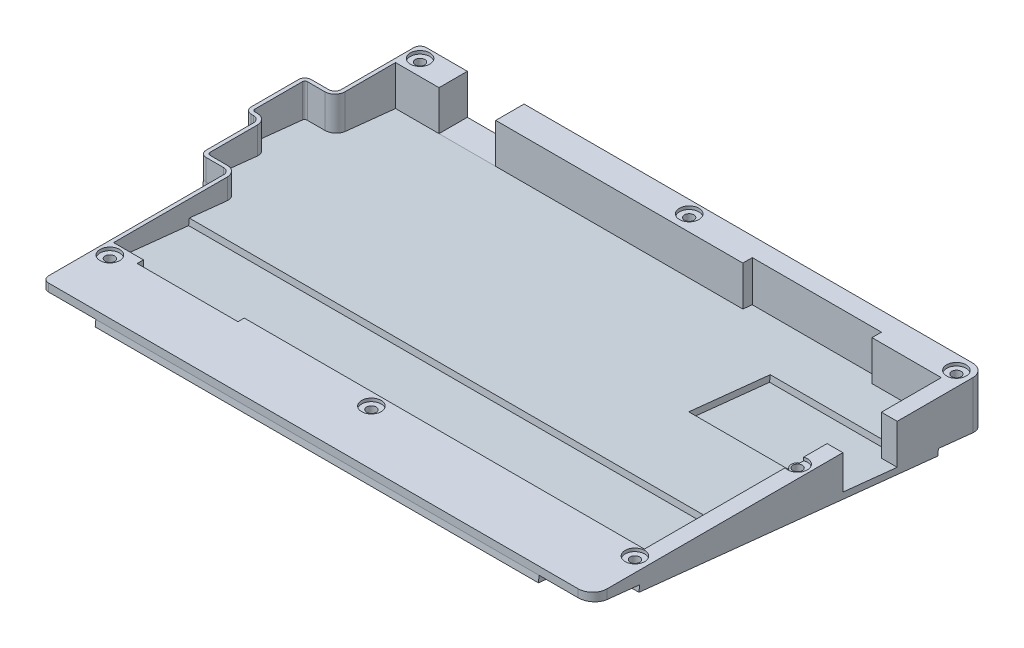
SolidWorks part; units mm, degrees
ref_plane "Front Plane" through (0, 0, 0) normal (0, 0, 1) x (1, 0, 0)
ref_plane "Top Plane" through (0, 0, 0) normal (0, 1, 0) x (1, 0, 0)
ref_plane "Right Plane" through (0, 0, 0) normal (1, 0, 0) x (0, 0, -1)
sketch "Sketch1" plane through (0, 0, 0) normal (0, 1, 0) x (1, 0, 0)
  line L0 (138.4196, 31.7518) -> (125.4196, 31.7518)
  line L1 (-35.0204, 31.7518) -> (107.4196, 31.7518)
  line L2 (140.4196, 29.7518) -> (140.4196, 6.7018)
  line L3 (-34.0204, 3.7518) -> (-34.0204, 22.7518)
  line L4 (136.4596, 27.7518) -> (136.4396, 27.7518)
  line L5 (142.4196, 4.7018) -> (147.9496, 4.7018)
  line L6 (-34.0204, 22.7518) -> (-12.0204, 22.7518)
  line L8 (149.9496, 2.7018) -> (149.9496, -12.3482)
  line L11 (147.9496, -14.3482) -> (147.1896, -14.3482)
  line L14 (145.1896, -16.3482) -> (145.1896, -31.3982)
  line L17 (143.1896, -33.3982) -> (137.6696, -33.3982)
  line L20 (135.6696, -35.3982) -> (135.6696, -77.4982)
  line L21 (-34.0204, -25.6003) -> (-34.0204, -71.4982)
  line L23 (133.6696, -79.4982) -> (-35.0204, -79.4982)
  line L28 (-39.0204, 27.7518) -> (-39.0204, 3.7518)
  line L31 (-34.0204, 3.7518) -> (-39.0204, 3.7518)
  line L32 (-34.0204, -13.4982) -> (-39.0204, -13.4982)
  line L33 (-39.0204, -75.4982) -> (-39.0204, -13.4982)
  line L34 (-34.0204, -71.4982) -> (92.9796, -71.4982)
  line L35 (92.9796, -71.4982) -> (92.9796, -73.4982)
  line L36 (92.9796, -73.4982) -> (124.9796, -73.4982)
  line L37 (124.9796, -73.4982) -> (124.9796, -71.4982)
  line L39 (134.4706, -35.3982) -> (134.4706, -71.4982)
  line L40 (134.4706, -71.4982) -> (124.9796, -71.4982)
  line L41 (137.6696, -32.1992) -> (143.1896, -32.1992)
  line L42 (-34.0204, -13.4982) -> (-34.0204, -22.1362)
  line L43 (143.9906, -31.3982) -> (143.9906, -16.3482)
  line L44 (-12.0204, 22.7518) -> (-12.0204, 25.7518)
  line L45 (147.1896, -13.1492) -> (147.9496, -13.1492)
  line L46 (148.7506, -12.3482) -> (148.7506, 2.7018)
  line L47 (-12.0204, 25.7518) -> (28.9796, 25.7518)
  line L48 (28.9796, 25.7518) -> (28.9796, 22.7518)
  line L49 (28.9796, 22.7518) -> (107.4196, 22.7518)
  line L50 (147.9496, 3.5027) -> (142.4196, 3.5027)
  line L51 (107.4196, 22.7518) -> (107.4196, 31.7518)
  line L52 (139.2206, 6.7018) -> (139.2206, 22.7518)
  line L53 (125.4196, 31.7518) -> (125.4196, 22.7518)
  line L54 (139.2206, 22.7518) -> (125.4196, 22.7518)
  arc A0 (138.4196, 31.7518) -> (140.4196, 29.7518) centre (138.4196, 29.7518) cw
  arc A1 (140.4196, 6.7018) -> (142.4196, 4.7018) centre (142.4196, 6.7018) ccw
  arc A2 (149.9496, 2.7018) -> (147.9496, 4.7018) centre (147.9496, 2.7018) ccw
  arc A3 (149.9496, -12.3482) -> (147.9496, -14.3482) centre (147.9496, -12.3482) cw
  arc A4 (147.1896, -14.3482) -> (145.1896, -16.3482) centre (147.1896, -16.3482) ccw
  arc A5 (145.1896, -31.3982) -> (143.1896, -33.3982) centre (143.1896, -31.3982) cw
  arc A6 (-35.0204, 31.7518) -> (-39.0204, 27.7518) centre (-35.0204, 27.7518) ccw
  arc A7 (-39.0204, -75.4982) -> (-35.0204, -79.4982) centre (-35.0204, -75.4982) ccw
  arc A8 (133.6696, -79.4982) -> (135.6696, -77.4982) centre (133.6696, -77.4982) ccw
  arc A9 (135.6696, -35.3982) -> (137.6696, -33.3982) centre (137.6696, -35.3982) cw
  circle A10 centre (-34.4204, 27.1518) radius 1.1
  circle A11 centre (51.0096, 27.7518) radius 1.1
  circle A12 centre (136.4396, 27.7518) radius 1.1
  circle A13 centre (-34.4204, -74.8982) radius 1.1
  circle A14 centre (48.6296, -75.4982) radius 1.1
  circle A15 centre (131.6496, -75.4982) radius 1.1
  circle A16 centre (-35.0204, -23.8682) radius 1.1
  arc A27 (-34.0204, -22.1362) -> (-34.0204, -25.6003) centre (-35.0204, -23.8682) cw
  arc A28 (139.2206, 6.7018) -> (142.4196, 3.5027) centre (142.4196, 6.7018) ccw
  arc A29 (147.9496, 3.5027) -> (148.7506, 2.7018) centre (147.9496, 2.7018) cw
  arc A30 (148.7506, -12.3482) -> (147.9496, -13.1492) centre (147.9496, -12.3482) cw
  arc A31 (147.1896, -13.1492) -> (143.9906, -16.3482) centre (147.1896, -16.3482) ccw
  arc A32 (143.9906, -31.3982) -> (143.1896, -32.1992) centre (143.1896, -31.3982) cw
  arc A33 (137.6696, -32.1992) -> (134.4706, -35.3982) centre (137.6696, -35.3982) ccw
extrude "Boss-Extrude2" add sketch "Sketch1" against normal blind 4.7 contours L41 A33 L39 L40 L37 L36 L35 L34 L21 A27 L42 L32 L33 A7 L23 A8 L20 A9 L17 A5 L14 A4 L11 A3 L8 A2 L5 A1 L2 A0 L0 L53 L54 L52 A28 L50 A29 L46 A30 L45 A31 L43 A32 A12 A13 A14 A15 | L1 A6 L28 L31 L3 L6 L44 L47 L48 L49 L51 A11 A10 region at (138.2833, 0, -29.6154) region at (31.7683, 0, -26.4895)
move or copy body "Body-Move/Copy1" bodies to move or copy 105 104 copy no rotation origin (55.4646, -2.35, 0) rotation axis (0, 0, 1) rotation angle 180
sketch "Sketch3" plane through (149.9496, 0, 0) normal (1, 0, 0) x (0, 0, -1)
  line L0 (-79.4982, 0) -> (-79.4982, -4.7) construction
  line L1 (-79.4982, 0) -> (-79.4982, -4.7)
  line L2 (31.7518, 0) -> (31.7518, -4.7) construction
  line L3 (31.7518, 0) -> (31.7518, -4.7)
  line L5 (-79.4982, -4.7) -> (31.7518, -16.3928)
  line L6 (31.7518, -16.3928) -> (31.7518, -4.7)
  line L7 (31.7518, -4.7) -> (-79.4982, -4.7)
  line M3 (-75.4982, -4.7) -> (-13.4982, -4.7)
  dimension "D1" = 6
extrude "Boss-Extrude3" add sketch "Sketch3" against normal up to surface (188.97 mm away) contours L6 L7 L5 M3 region at (149.9496, -8.5976, 5.3315) up to face at (-39.0204, -2.35, 4.8232)
sketch "Sketch4" plane through (0, -4.7, 0) normal (0, 1, 0) x (1, 0, 0)
  line L2 (145.9496, -79.4982) -> (149.9496, -79.4982)
  line L3 (149.9496, -79.4982) -> (149.9496, -75.4982)
  line L4 (-29.4904, 6.7018) -> (-29.4904, 29.7518)
  line L5 (-27.4904, 31.7518) -> (-39.0204, 31.7518)
  line L6 (-36.2604, -14.3482) -> (-37.0204, -14.3482)
  line L7 (-39.0204, -12.3482) -> (-39.0204, -79.4982)
  line L8 (-39.0204, -79.4982) -> (-22.7404, -79.4982)
  line L9 (-24.7404, -77.4982) -> (-24.7404, -35.3982)
  line L10 (-26.7404, -33.3982) -> (-32.2604, -33.3982)
  line L11 (-34.2604, -31.3982) -> (-34.2604, -16.3482)
  line L12 (-36.2604, -14.3482) -> (-37.0204, -14.3482)
  line L13 (-39.0204, -12.3482) -> (-39.0204, -79.4982)
  line L14 (-39.0204, -79.4982) -> (-22.7404, -79.4982)
  line L15 (-24.7404, -77.4982) -> (-24.7404, -35.3982)
  line L16 (-26.7404, -33.3982) -> (-32.2604, -33.3982)
  line L17 (-34.2604, -31.3982) -> (-34.2604, -16.3482)
  line L18 (-39.0204, 31.7518) -> (-39.0204, 2.7018)
  line L19 (-37.0204, 4.7018) -> (-31.4904, 4.7018)
  line L20 (-29.4904, 6.7018) -> (-29.4904, 29.7518)
  line L21 (-27.4904, 31.7518) -> (-39.0204, 31.7518)
  line L22 (-39.0204, 31.7518) -> (-39.0204, 2.7018)
  line L23 (-37.0204, 4.7018) -> (-31.4904, 4.7018)
  line L24 (145.9496, -79.4982) -> (149.9496, -79.4982)
  line L25 (149.9496, -79.4982) -> (149.9496, -75.4982)
  line L26 (149.9496, 31.7518) -> (145.9496, 31.7518)
  line L27 (149.9496, 27.7518) -> (149.9496, 31.7518)
  line L28 (149.9496, 31.7518) -> (145.9496, 31.7518)
  line L29 (149.9496, 27.7518) -> (149.9496, 31.7518)
  arc A1 (145.9496, -79.4982) -> (149.9496, -75.4982) centre (145.9496, -75.4982) ccw
  arc A2 (145.9496, -79.4982) -> (149.9496, -75.4982) centre (145.9496, -75.4982) ccw
  arc A3 (-27.4904, 31.7518) -> (-29.4904, 29.7518) centre (-27.4904, 29.7518) ccw
  arc A4 (-37.0204, 4.7018) -> (-39.0204, 2.7018) centre (-37.0204, 2.7018) ccw
  arc A5 (-39.0204, -12.3482) -> (-37.0204, -14.3482) centre (-37.0204, -12.3482) ccw
  arc A6 (-24.7404, -77.4982) -> (-22.7404, -79.4982) centre (-22.7404, -77.4982) ccw
  arc A7 (-24.7404, -35.3982) -> (-26.7404, -33.3982) centre (-26.7404, -35.3982) ccw
  arc A8 (-34.2604, -31.3982) -> (-32.2604, -33.3982) centre (-32.2604, -31.3982) ccw
  arc A9 (-34.2604, -16.3482) -> (-36.2604, -14.3482) centre (-36.2604, -16.3482) ccw
  arc A10 (-39.0204, -12.3482) -> (-37.0204, -14.3482) centre (-37.0204, -12.3482) ccw
  arc A11 (-24.7404, -77.4982) -> (-22.7404, -79.4982) centre (-22.7404, -77.4982) ccw
  arc A12 (-24.7404, -35.3982) -> (-26.7404, -33.3982) centre (-26.7404, -35.3982) ccw
  arc A13 (-34.2604, -31.3982) -> (-32.2604, -33.3982) centre (-32.2604, -31.3982) ccw
  arc A14 (-34.2604, -16.3482) -> (-36.2604, -14.3482) centre (-36.2604, -16.3482) ccw
  arc A15 (-31.4904, 4.7018) -> (-29.4904, 6.7018) centre (-31.4904, 6.7018) ccw
  arc A16 (-27.4904, 31.7518) -> (-29.4904, 29.7518) centre (-27.4904, 29.7518) ccw
  arc A17 (-37.0204, 4.7018) -> (-39.0204, 2.7018) centre (-37.0204, 2.7018) ccw
  arc A18 (-31.4904, 4.7018) -> (-29.4904, 6.7018) centre (-31.4904, 6.7018) ccw
  arc A19 (149.9496, 27.7518) -> (145.9496, 31.7518) centre (145.9496, 27.7518) ccw
  arc A20 (149.9496, 27.7518) -> (145.9496, 31.7518) centre (145.9496, 27.7518) ccw
  dimension "D1" = 0
  dimension "D2" = 0
  dimension "D3" = 0
  dimension "D4" = 0
extrude "Cut-Extrude1" cut sketch "Sketch4" against normal through all
ref_plane "Plane4" through (0, 15, 0) normal (0, 1, 0) x (1, 0, 0)
sketch "Sketch10" plane through (0, 15, 0) normal (0, 1, 0) x (1, 0, 0)
  line L0 (-14.4904, 22.7518) -> (3.5096, 22.7518)
  line L1 (144.9496, 3.7518) -> (144.9496, -13.4982)
  line L27 (-14.4904, 31.7518) -> (-14.4904, 22.7518)
  line L28 (-14.4904, 22.7518) -> (-28.2913, 22.7518)
  line L29 (-28.2913, 22.7518) -> (-28.2913, 6.7018)
  line L30 (-31.4904, 3.5027) -> (-37.0204, 3.5027)
  line L31 (-37.8213, 2.7018) -> (-37.8213, -12.3482)
  line L32 (-37.0204, -13.1492) -> (-36.2604, -13.1492)
  line L33 (-33.0613, -16.3482) -> (-33.0613, -31.3982)
  line L34 (-32.2604, -32.1992) -> (-26.7404, -32.1992)
  line L35 (-23.5413, -35.3982) -> (-23.5413, -71.4982)
  line L36 (-23.5413, -71.4982) -> (-14.0504, -71.4982)
  line L37 (-14.0504, -71.4982) -> (-14.0504, -73.4982)
  line L38 (-14.0504, -73.4982) -> (17.9496, -73.4982)
  line L39 (17.9496, -73.4982) -> (17.9496, -71.4982)
  line L40 (17.9496, -71.4982) -> (144.9496, -71.4982)
  line L41 (144.9496, -71.4982) -> (144.9496, -25.6003)
  line L42 (144.9496, -22.1362) -> (144.9496, -13.4982)
  line L43 (144.9496, -13.4982) -> (149.9496, -13.4982)
  line L44 (149.9496, -13.4982) -> (149.9496, 3.7518)
  line L45 (149.9496, 3.7518) -> (144.9496, 3.7518)
  line L46 (144.9496, 3.7518) -> (144.9496, 22.7518)
  line L47 (144.9496, 22.7518) -> (122.9496, 22.7518)
  line L48 (122.9496, 22.7518) -> (122.9496, 25.7518)
  line L49 (122.9496, 25.7518) -> (81.9496, 25.7518)
  line L50 (81.9496, 25.7518) -> (81.9496, 22.7518)
  line L51 (81.9496, 22.7518) -> (3.5096, 22.7518)
  line L52 (3.5096, 22.7518) -> (3.5096, 31.7518)
  line L53 (3.5096, 31.7518) -> (-14.4904, 31.7518)
  line L54 (-14.4904, 31.7518) -> (-14.4904, 22.7518)
  line L55 (-14.4904, 22.7518) -> (-28.2913, 22.7518)
  line L56 (-28.2913, 22.7518) -> (-28.2913, 6.7018)
  line L57 (-31.4904, 3.5027) -> (-37.0204, 3.5027)
  line L58 (-37.8213, 2.7018) -> (-37.8213, -12.3482)
  line L59 (-37.0204, -13.1492) -> (-36.2604, -13.1492)
  line L60 (-33.0613, -16.3482) -> (-33.0613, -31.3982)
  line L61 (-32.2604, -32.1992) -> (-26.7404, -32.1992)
  line L62 (-23.5413, -35.3982) -> (-23.5413, -71.4982)
  line L63 (-23.5413, -71.4982) -> (-14.0504, -71.4982)
  line L64 (-14.0504, -71.4982) -> (-14.0504, -73.4982)
  line L65 (-14.0504, -73.4982) -> (17.9496, -73.4982)
  line L66 (17.9496, -73.4982) -> (17.9496, -71.4982)
  line L67 (17.9496, -71.4982) -> (144.9496, -71.4982)
  line L68 (144.9496, -71.4982) -> (144.9496, -25.6003)
  line L69 (144.9496, -22.1362) -> (144.9496, -13.4982)
  line L70 (144.9496, -13.4982) -> (149.9496, -13.4982)
  line L71 (149.9496, -13.4982) -> (149.9496, 3.7518)
  line L72 (149.9496, 3.7518) -> (144.9496, 3.7518)
  line L73 (144.9496, 3.7518) -> (144.9496, 22.7518)
  line L74 (144.9496, 22.7518) -> (122.9496, 22.7518)
  line L75 (122.9496, 22.7518) -> (122.9496, 25.7518)
  line L76 (122.9496, 25.7518) -> (81.9496, 25.7518)
  line L77 (81.9496, 25.7518) -> (81.9496, 22.7518)
  line L78 (81.9496, 22.7518) -> (3.5096, 22.7518)
  line L79 (3.5096, 22.7518) -> (3.5096, 31.7518)
  line L80 (3.5096, 31.7518) -> (-14.4904, 31.7518)
  arc A7 (-31.4904, 3.5027) -> (-28.2913, 6.7018) centre (-31.4904, 6.7018) ccw
  arc A8 (-37.0204, 3.5027) -> (-37.8213, 2.7018) centre (-37.0204, 2.7018) ccw
  arc A9 (-37.8213, -12.3482) -> (-37.0204, -13.1492) centre (-37.0204, -12.3482) ccw
  arc A10 (-33.0613, -16.3482) -> (-36.2604, -13.1492) centre (-36.2604, -16.3482) ccw
  arc A11 (-33.0613, -31.3982) -> (-32.2604, -32.1992) centre (-32.2604, -31.3982) ccw
  arc A12 (-23.5413, -35.3982) -> (-26.7404, -32.1992) centre (-26.7404, -35.3982) ccw
  arc A13 (144.9496, -22.1362) -> (144.9496, -25.6003) centre (145.9496, -23.8682) ccw
  arc A14 (-31.4904, 3.5027) -> (-28.2913, 6.7018) centre (-31.4904, 6.7018) ccw
  arc A15 (-37.0204, 3.5027) -> (-37.8213, 2.7018) centre (-37.0204, 2.7018) ccw
  arc A16 (-37.8213, -12.3482) -> (-37.0204, -13.1492) centre (-37.0204, -12.3482) ccw
  arc A17 (-33.0613, -16.3482) -> (-36.2604, -13.1492) centre (-36.2604, -16.3482) ccw
  arc A18 (-33.0613, -31.3982) -> (-32.2604, -32.1992) centre (-32.2604, -31.3982) ccw
  arc A19 (-23.5413, -35.3982) -> (-26.7404, -32.1992) centre (-26.7404, -35.3982) ccw
  arc A20 (144.9496, -22.1362) -> (144.9496, -25.6003) centre (145.9496, -23.8682) ccw
  dimension "D1" = 0
extrude "Cut-Extrude2" cut sketch "Sketch10" against normal through all contours A20 L69 L1 L73 L74 L75 L76 L77 L78 L0 L55 L56 A14 L57 A15 L58 A16 L59 A17 L60 A18 L61 A19 L62 L63 L64 L65 L66 L67 L68 region at (57.9798, 15, 23.6888)
sketch "Sketch11" plane through (144.9496, 0, 0) normal (-1, 0, 0) x (0, 0, 1)
  line L0 (-22.7518, -15.4469) -> (71.4982, -5.5408)
  line L1 (71.4982, -5.5408) -> (71.4982, -3.5408)
  line L2 (71.4982, 0) -> (71.4982, -5.5408) construction
  line L3 (71.4982, -3.5408) -> (-22.7518, -13.4469)
  line L4 (-22.7518, 0) -> (-22.7518, -15.4469) construction
  line L5 (-22.7518, -13.4469) -> (-22.7518, -15.4469)
  dimension "D1" = 2
  dimension "D2" = 2
extrude "Boss-Extrude4" add sketch "Sketch11" along normal up to surface (182.7709 mm away)
sketch "Sketch12" plane through (0, -10.9348, 1.1493) normal (0, 0.9945, -0.1045) x (1, 0, 0)
  line L0 (-29.4904, 7.8943) -> (-29.4904, 24.0327) construction
  line L1 (-29.4904, 24.0327) -> (-37.8213, 24.0327) construction
  line L2 (-37.8213, 24.0327) -> (-37.8213, 5.715) construction
  line L3 (-37.0204, 5.8833) -> (-31.4904, 5.8833) construction
  line L4 (-36.2604, -13.2716) -> (-37.0204, -13.2716) construction
  line L5 (-37.8213, -13.1033) -> (-37.8213, -70.7364) construction
  line L6 (-37.8213, -70.7364) -> (-24.7404, -70.7364) construction
  line L7 (-24.7404, -70.7364) -> (-24.7404, -34.4376) construction
  line L8 (-26.7404, -32.4266) -> (-32.2604, -32.4266) construction
  line L9 (-34.2604, -30.4155) -> (-34.2604, -15.2826) construction
  line L10 (-29.4904, 7.8943) -> (-29.4904, 24.0327)
  line L11 (-29.4904, 24.0327) -> (-37.8213, 24.0327)
  line L12 (-37.8213, 24.0327) -> (-37.8213, 5.715)
  line L13 (-37.0204, 5.8833) -> (-31.4904, 5.8833)
  line L14 (-36.2604, -13.2716) -> (-37.0204, -13.2716)
  line L15 (-37.8213, -13.1033) -> (-37.8213, -70.7364)
  line L16 (-37.8213, -70.7364) -> (-24.7404, -70.7364)
  line L17 (-24.7404, -70.7364) -> (-24.7404, -34.4376)
  line L18 (-26.7404, -32.4266) -> (-32.2604, -32.4266)
  line L19 (-34.2604, -30.4155) -> (-34.2604, -15.2826)
  line L20 (-37.8213, 24.0327) -> (-37.8213, 25.9101)
  line L21 (-29.4904, 24.0327) -> (-29.4904, 27.1127)
  line L22 (-29.4904, 27.1127) -> (-37.8213, 25.9101)
  ellipse E0 centre (-31.4904, 7.8943) end of major axis (-31.4904, 9.9053) minor radius 2 (-31.4904, 5.8833) -> (-29.4904, 7.8943) ccw construction
  ellipse E1 centre (-37.0204, 3.8723) end of major axis (-37.0204, 5.8833) minor radius 2 (-37.0204, 5.8833) -> (-37.8213, 5.715) ccw construction
  ellipse E2 centre (-37.0204, -11.2606) end of major axis (-37.0204, -9.2496) minor radius 2 (-37.8213, -13.1033) -> (-37.0204, -13.2716) ccw construction
  ellipse E3 centre (-26.7404, -34.4376) end of major axis (-26.7404, -32.4266) minor radius 2 (-24.7404, -34.4376) -> (-26.7404, -32.4266) ccw construction
  ellipse E4 centre (-32.2604, -30.4155) end of major axis (-32.2604, -28.4045) minor radius 2 (-34.2604, -30.4155) -> (-32.2604, -32.4266) ccw construction
  ellipse E5 centre (-36.2604, -15.2826) end of major axis (-36.2604, -13.2716) minor radius 2 (-34.2604, -15.2826) -> (-36.2604, -13.2716) ccw construction
  ellipse E6 centre (-31.4904, 7.8943) end of major axis (-31.4904, 9.9053) minor radius 2 (-31.4904, 5.8833) -> (-29.4904, 7.8943) ccw
  ellipse E7 centre (-37.0204, 3.8723) end of major axis (-37.0204, 5.8833) minor radius 2 (-37.0204, 5.8833) -> (-37.8213, 5.715) ccw
  ellipse E8 centre (-37.0204, -11.2606) end of major axis (-37.0204, -9.2496) minor radius 2 (-37.8213, -13.1033) -> (-37.0204, -13.2716) ccw
  ellipse E9 centre (-26.7404, -34.4376) end of major axis (-26.7404, -32.4266) minor radius 2 (-24.7404, -34.4376) -> (-26.7404, -32.4266) ccw
  ellipse E10 centre (-32.2604, -30.4155) end of major axis (-32.2604, -28.4045) minor radius 2 (-34.2604, -30.4155) -> (-32.2604, -32.4266) ccw
  ellipse E11 centre (-36.2604, -15.2826) end of major axis (-36.2604, -13.2716) minor radius 2 (-34.2604, -15.2826) -> (-36.2604, -13.2716) ccw
sketch "Sketch26" plane through (-37.8213, 0, 0) normal (-1, 0, 0) x (0, 0, 1)
  line L0 (14.1808, -9.5651) -> (-4.5344, -11.5322)
  line L1 (-4.5344, -13.5322) -> (14.1808, -11.5651)
  line L4 (-22.7518, -15.4469) -> (-4.5344, -13.5322)
  line L5 (-4.5344, -13.5322) -> (-4.5344, -11.5322)
  line L6 (-4.5344, -11.5322) -> (-22.7518, -13.4469)
  line L7 (-22.7518, -13.4469) -> (-22.7518, -15.4469)
  line L8 (-22.7518, -15.4469) -> (-4.5344, -13.5322)
  line L9 (-4.5344, -13.5322) -> (-4.5344, -11.5322)
  line L10 (-4.5344, -11.5322) -> (-22.7518, -13.4469)
  line L11 (-22.7518, -13.4469) -> (-22.7518, -15.4469)
  line L12 (14.1808, -9.5651) -> (14.1808, -11.5651)
  line L13 (14.1808, -11.5651) -> (71.4982, -5.5408)
  line L14 (71.4982, -5.5408) -> (71.4982, -3.5408)
  line L15 (71.4982, -3.5408) -> (14.1808, -9.5651)
  line L16 (14.1808, -9.5651) -> (14.1808, -11.5651)
  line L17 (14.1808, -11.5651) -> (71.4982, -5.5408)
  line L18 (71.4982, -5.5408) -> (71.4982, -3.5408)
  line L19 (71.4982, -3.5408) -> (14.1808, -9.5651)
  line M9 (14.1808, -9.5651) -> (14.1808, -11.5651)
  line M10 (14.1808, -11.5651) -> (71.4982, -5.5408)
  line M11 (71.4982, -5.5408) -> (71.4982, -3.5408)
  line M12 (71.4982, -3.5408) -> (14.1808, -9.5651)
  dimension "D1" = 0
  dimension "D2" = 0
extrude "Boss-Extrude10" add sketch "Sketch26" along normal blind 11 contours L10 L11 L8 L9 | L9 L1 L0 M9 | M12 M9 M10 M11 region at (-37.8213, -11.5487, 4.8232) region at (-37.8213, -7.553, 42.8395) region at (-37.8213, -13.4895, -13.6431)
sketch "Sketch28" plane through (0, -10.9348, 1.1493) normal (0, 0.9945, -0.1045) x (1, 0, 0)
  line L0 (-48.8213, 24.0327) -> (-52.7132, 28.3929)
  line L1 (-52.7132, 28.3929) -> (-29.4904, 30.8021)
  line L2 (-29.4904, 30.8021) -> (-29.4904, 24.0327)
  line L10 (-29.4904, 7.8943) -> (-29.4904, 24.0327)
  line L11 (-29.4904, 24.0327) -> (-48.8213, 24.0327)
  line L12 (-48.8213, 24.0327) -> (-48.8213, -70.7364)
  line L13 (-48.8213, -70.7364) -> (-24.7404, -70.7364)
  line L14 (-24.7404, -70.7364) -> (-24.7404, -34.4376)
  line L15 (-26.7404, -32.4266) -> (-32.2604, -32.4266)
  line L16 (-34.2604, -30.4155) -> (-34.2604, -15.2826)
  line L17 (-36.2604, -13.2716) -> (-37.0204, -13.2716)
  line L18 (-39.0204, -11.2606) -> (-39.0204, 3.8723)
  line L19 (-37.0204, 5.8833) -> (-31.4904, 5.8833)
  line L20 (-29.4904, 7.8943) -> (-29.4904, 24.0327)
  line L21 (-29.4904, 24.0327) -> (-48.8213, 24.0327)
  line L22 (-48.8213, 24.0327) -> (-48.8213, -70.7364)
  line L23 (-48.8213, -70.7364) -> (-24.7404, -70.7364)
  line L24 (-24.7404, -70.7364) -> (-24.7404, -34.4376)
  line L25 (-26.7404, -32.4266) -> (-32.2604, -32.4266)
  line L26 (-34.2604, -30.4155) -> (-34.2604, -15.2826)
  line L27 (-36.2604, -13.2716) -> (-37.0204, -13.2716)
  line L28 (-39.0204, -11.2606) -> (-39.0204, 3.8723)
  line L29 (-37.0204, 5.8833) -> (-31.4904, 5.8833)
  ellipse E6 centre (-31.4904, 7.8943) end of major axis (-31.4904, 9.9053) minor radius 2 (-31.4904, 5.8833) -> (-29.4904, 7.8943) ccw
  ellipse E7 centre (-26.7404, -34.4376) end of major axis (-26.7404, -32.4266) minor radius 2 (-24.7404, -34.4376) -> (-26.7404, -32.4266) ccw
  ellipse E8 centre (-32.2604, -30.4155) end of major axis (-32.2604, -28.4045) minor radius 2 (-34.2604, -30.4155) -> (-32.2604, -32.4266) ccw
  ellipse E9 centre (-36.2604, -15.2826) end of major axis (-36.2604, -13.2716) minor radius 2 (-34.2604, -15.2826) -> (-36.2604, -13.2716) ccw
  ellipse E10 centre (-37.0204, -11.2606) end of major axis (-37.0204, -9.2496) minor radius 2 (-39.0204, -11.2606) -> (-37.0204, -13.2716) ccw
  ellipse E11 centre (-37.0204, 3.8723) end of major axis (-37.0204, 5.8833) minor radius 2 (-37.0204, 5.8833) -> (-39.0204, 3.8723) ccw
  ellipse E12 centre (-31.4904, 7.8943) end of major axis (-31.4904, 9.9053) minor radius 2 (-31.4904, 5.8833) -> (-29.4904, 7.8943) ccw
  ellipse E13 centre (-26.7404, -34.4376) end of major axis (-26.7404, -32.4266) minor radius 2 (-24.7404, -34.4376) -> (-26.7404, -32.4266) ccw
  ellipse E14 centre (-32.2604, -30.4155) end of major axis (-32.2604, -28.4045) minor radius 2 (-34.2604, -30.4155) -> (-32.2604, -32.4266) ccw
  ellipse E15 centre (-36.2604, -15.2826) end of major axis (-36.2604, -13.2716) minor radius 2 (-34.2604, -15.2826) -> (-36.2604, -13.2716) ccw
  ellipse E16 centre (-37.0204, -11.2606) end of major axis (-37.0204, -9.2496) minor radius 2 (-39.0204, -11.2606) -> (-37.0204, -13.2716) ccw
  ellipse E17 centre (-37.0204, 3.8723) end of major axis (-37.0204, 5.8833) minor radius 2 (-37.0204, 5.8833) -> (-39.0204, 3.8723) ccw
  ellipse M17 centre (-31.4904, 7.8943) end of major axis (-31.4904, 9.9053) minor radius 2 (-31.4904, 5.8833) -> (-29.4904, 7.8943) ccw
  line M18 (-29.4904, 7.8943) -> (-29.4904, 24.0327)
  line M19 (-29.4904, 24.0327) -> (-48.8213, 24.0327)
  line M20 (-48.8213, 24.0327) -> (-48.8213, -70.7364)
  line M21 (-48.8213, -70.7364) -> (-24.7404, -70.7364)
  line M22 (-24.7404, -70.7364) -> (-24.7404, -34.4376)
  ellipse M23 centre (-26.7404, -34.4376) end of major axis (-26.7404, -32.4266) minor radius 2 (-24.7404, -34.4376) -> (-26.7404, -32.4266) ccw
  line M24 (-26.7404, -32.4266) -> (-32.2604, -32.4266)
  ellipse M25 centre (-32.2604, -30.4155) end of major axis (-32.2604, -28.4045) minor radius 2 (-32.2604, -32.4266) -> (-34.2604, -30.4155) cw
  line M26 (-34.2604, -30.4155) -> (-34.2604, -15.2826)
  ellipse M27 centre (-36.2604, -15.2826) end of major axis (-36.2604, -13.2716) minor radius 2 (-34.2604, -15.2826) -> (-36.2604, -13.2716) ccw
  line M28 (-36.2604, -13.2716) -> (-37.0204, -13.2716)
  ellipse M29 centre (-37.0204, -11.2606) end of major axis (-37.0204, -9.2496) minor radius 2 (-37.0204, -13.2716) -> (-39.0204, -11.2606) cw
  line M30 (-39.0204, -11.2606) -> (-39.0204, 3.8723)
  ellipse M31 centre (-37.0204, 3.8723) end of major axis (-37.0204, 5.8833) minor radius 2 (-39.0204, 3.8723) -> (-37.0204, 5.8833) cw
  line M32 (-37.0204, 5.8833) -> (-31.4904, 5.8833)
  dimension "D1" = 0
extrude "Cut-Extrude8" cut sketch "Sketch28" against normal blind 11 contours M32 M17 M18 M19 M20 M21 M22 M23 M24 M25 M26 M27 M28 M29 M30 M31 | L2 L1 L0 M19 region at (-39.4803, -13.7524, -25.6581) region at (-38.8035, -7.967, 29.3861)
sketch "Sketch30" plane through (122.9496, 0, 0) normal (-1, 0, 0) x (0, 0, 1)
  line L0 (-25.7518, -15.7622) -> (-22.7518, -15.4469)
  line L1 (-22.7518, -15.4469) -> (-22.7518, -13.4469)
  line L2 (-22.7518, -15.4469) -> (-22.7518, -13.4469) construction
  line L3 (-22.7518, -13.4469) -> (-25.7518, -13.7622)
  line L4 (-25.7518, 0) -> (-25.7518, -15.7622) construction
  line L5 (-25.7518, -13.7622) -> (-25.7518, -15.7622)
extrude "Boss-Extrude11" add sketch "Sketch30" along normal up to surface (41 mm away)
sketch "Sketch32" plane through (17.9496, 0, 0) normal (-1, 0, 0) x (0, 0, 1)
  line L0 (73.4982, -5.3306) -> (71.4982, -5.5408)
  line L1 (71.4982, -5.5408) -> (71.4982, -3.5408)
  line L2 (71.4982, -3.5408) -> (73.4982, -3.3306)
  line L3 (73.4982, 0) -> (73.4982, -5.3306) construction
  line L4 (73.4982, -3.3306) -> (73.4982, -5.3306)
  dimension "D1" = 2
extrude "Boss-Extrude14" add sketch "Sketch32" along normal up to surface (32 mm away)
sketch "Sketch35" plane through (0, 0, 0) normal (0, 1, 0) x (1, 0, 0)
  line L0 (149.9496, 3.7518) -> (149.9496, -13.4982)
  line L1 (149.9496, -13.4982) -> (144.9496, -13.4982)
  line L2 (144.9496, -13.4982) -> (144.9496, 3.7518)
  line L3 (144.9496, 3.7518) -> (149.9496, 3.7518)
ref_plane "Plane5" through (149.9496, -5.1204, 75.4982) normal (0, -1, 0) x (-1, 0, 0)
sketch "Sketch47" plane through (0, 0, 0) normal (0, 1, 0) x (1, 0, 0)
  circle A0 centre (145.3496, -74.8982) radius 3.1
  circle A1 centre (62.2996, -75.4982) radius 3.1
  circle A2 centre (-20.7204, -75.4982) radius 3.1
  circle A3 centre (-25.5104, 27.7518) radius 3.1
  circle A4 centre (59.9196, 27.7518) radius 3.1
  circle A5 centre (145.3496, 27.1518) radius 3.1
  circle A6 centre (145.9496, -23.8682) radius 3.1
extrude "Cut-Extrude17" cut sketch "Sketch47" against normal blind 1.8
sketch "Sketch48" plane through (0, 0, 0) normal (0, 1, 0) x (1, 0, 0)
  line L10 (145.9496, 31.7518) -> (3.5096, 31.7518)
  line L11 (3.5096, 31.7518) -> (3.5096, 22.7518)
  line L12 (3.5096, 22.7518) -> (81.9496, 22.7518)
  line L13 (81.9496, 22.7518) -> (81.9496, 25.7518)
  line L14 (81.9496, 25.7518) -> (122.9496, 25.7518)
  line L15 (122.9496, 25.7518) -> (122.9496, 22.7518)
  line L16 (122.9496, 22.7518) -> (144.9496, 22.7518)
  line L17 (144.9496, 22.7518) -> (144.9496, 3.7518)
  line L18 (144.9496, 3.7518) -> (149.9496, 3.7518)
  line L19 (149.9496, 3.7518) -> (149.9496, 27.7518)
  line L20 (145.9496, 31.7518) -> (3.5096, 31.7518)
  line L21 (3.5096, 31.7518) -> (3.5096, 22.7518)
  line L22 (3.5096, 22.7518) -> (81.9496, 22.7518)
  line L23 (81.9496, 22.7518) -> (81.9496, 25.7518)
  line L24 (81.9496, 25.7518) -> (122.9496, 25.7518)
  line L25 (122.9496, 25.7518) -> (122.9496, 22.7518)
  line L26 (122.9496, 22.7518) -> (144.9496, 22.7518)
  line L27 (144.9496, 22.7518) -> (144.9496, 3.7518)
  line L28 (144.9496, 3.7518) -> (149.9496, 3.7518)
  line L29 (149.9496, 3.7518) -> (149.9496, 27.7518)
  line L47 (144.9496, -13.4982) -> (144.9496, -20.9339)
  line L48 (144.9496, -26.8025) -> (144.9496, -71.4982)
  line L49 (144.9496, -71.4982) -> (17.9496, -71.4982)
  line L50 (17.9496, -71.4982) -> (17.9496, -73.4982)
  line L51 (17.9496, -73.4982) -> (-14.0504, -73.4982)
  line L52 (-14.0504, -73.4982) -> (-14.0504, -71.4982)
  line L53 (-14.0504, -71.4982) -> (-23.5413, -71.4982)
  line L54 (-23.5413, -71.4982) -> (-23.5413, -35.3982)
  line L55 (-26.7404, -32.1992) -> (-32.2604, -32.1992)
  line L56 (-33.0613, -31.3982) -> (-33.0613, -16.3482)
  line L57 (-36.2604, -13.1492) -> (-37.0204, -13.1492)
  line L58 (-37.8213, -12.3482) -> (-37.8213, 2.7018)
  line L59 (-37.0204, 3.5027) -> (-31.4904, 3.5027)
  line L60 (-28.2913, 6.7018) -> (-28.2913, 22.7518)
  line L61 (-28.2913, 22.7518) -> (-14.4904, 22.7518)
  line L62 (-14.4904, 22.7518) -> (-14.4904, 31.7518)
  line L63 (-14.4904, 31.7518) -> (-27.4904, 31.7518)
  line L64 (-29.4904, 29.7518) -> (-29.4904, 6.7018)
  line L65 (-31.4904, 4.7018) -> (-37.0204, 4.7018)
  line L66 (-39.0204, 2.7018) -> (-39.0204, -12.3482)
  line L67 (-37.0204, -14.3482) -> (-36.2604, -14.3482)
  line L68 (-34.2604, -16.3482) -> (-34.2604, -31.3982)
  line L69 (-32.2604, -33.3982) -> (-26.7404, -33.3982)
  line L70 (-24.7404, -35.3982) -> (-24.7404, -77.4982)
  line L71 (-22.7404, -79.4982) -> (145.9496, -79.4982)
  line L72 (149.9496, -75.4982) -> (149.9496, -13.4982)
  line L73 (149.9496, -13.4982) -> (144.9496, -13.4982)
  line L74 (144.9496, -13.4982) -> (144.9496, -20.9339)
  line L75 (144.9496, -26.8025) -> (144.9496, -71.4982)
  line L76 (144.9496, -71.4982) -> (17.9496, -71.4982)
  line L77 (17.9496, -71.4982) -> (17.9496, -73.4982)
  line L78 (17.9496, -73.4982) -> (-14.0504, -73.4982)
  line L79 (-14.0504, -73.4982) -> (-14.0504, -71.4982)
  line L80 (-14.0504, -71.4982) -> (-23.5413, -71.4982)
  line L81 (-23.5413, -71.4982) -> (-23.5413, -35.3982)
  line L82 (-26.7404, -32.1992) -> (-32.2604, -32.1992)
  line L83 (-33.0613, -31.3982) -> (-33.0613, -16.3482)
  line L84 (-36.2604, -13.1492) -> (-37.0204, -13.1492)
  line L85 (-37.8213, -12.3482) -> (-37.8213, 2.7018)
  line L86 (-37.0204, 3.5027) -> (-31.4904, 3.5027)
  line L87 (-28.2913, 6.7018) -> (-28.2913, 22.7518)
  line L88 (-28.2913, 22.7518) -> (-14.4904, 22.7518)
  line L89 (-14.4904, 22.7518) -> (-14.4904, 31.7518)
  line L90 (-14.4904, 31.7518) -> (-27.4904, 31.7518)
  line L91 (-29.4904, 29.7518) -> (-29.4904, 6.7018)
  line L92 (-31.4904, 4.7018) -> (-37.0204, 4.7018)
  line L93 (-39.0204, 2.7018) -> (-39.0204, -12.3482)
  line L94 (-37.0204, -14.3482) -> (-36.2604, -14.3482)
  line L95 (-34.2604, -16.3482) -> (-34.2604, -31.3982)
  line L96 (-32.2604, -33.3982) -> (-26.7404, -33.3982)
  line L97 (-24.7404, -35.3982) -> (-24.7404, -77.4982)
  line L98 (-22.7404, -79.4982) -> (145.9496, -79.4982)
  line L99 (149.9496, -75.4982) -> (149.9496, -13.4982)
  line L100 (149.9496, -13.4982) -> (144.9496, -13.4982)
  arc A1 (149.9496, 27.7518) -> (145.9496, 31.7518) centre (145.9496, 27.7518) ccw
  arc A2 (149.9496, 27.7518) -> (145.9496, 31.7518) centre (145.9496, 27.7518) ccw
  arc A18 (144.9496, -26.8025) -> (144.9496, -20.9339) centre (145.9496, -23.8682) ccw
  arc A19 (-23.5413, -35.3982) -> (-26.7404, -32.1992) centre (-26.7404, -35.3982) ccw
  arc A20 (-33.0613, -31.3982) -> (-32.2604, -32.1992) centre (-32.2604, -31.3982) ccw
  arc A21 (-33.0613, -16.3482) -> (-36.2604, -13.1492) centre (-36.2604, -16.3482) ccw
  arc A22 (-37.8213, -12.3482) -> (-37.0204, -13.1492) centre (-37.0204, -12.3482) ccw
  arc A23 (-37.0204, 3.5027) -> (-37.8213, 2.7018) centre (-37.0204, 2.7018) ccw
  arc A24 (-31.4904, 3.5027) -> (-28.2913, 6.7018) centre (-31.4904, 6.7018) ccw
  arc A25 (-27.4904, 31.7518) -> (-29.4904, 29.7518) centre (-27.4904, 29.7518) ccw
  arc A26 (-31.4904, 4.7018) -> (-29.4904, 6.7018) centre (-31.4904, 6.7018) ccw
  arc A27 (-37.0204, 4.7018) -> (-39.0204, 2.7018) centre (-37.0204, 2.7018) ccw
  arc A28 (-39.0204, -12.3482) -> (-37.0204, -14.3482) centre (-37.0204, -12.3482) ccw
  arc A29 (-34.2604, -16.3482) -> (-36.2604, -14.3482) centre (-36.2604, -16.3482) ccw
  arc A30 (-34.2604, -31.3982) -> (-32.2604, -33.3982) centre (-32.2604, -31.3982) ccw
  arc A31 (-24.7404, -35.3982) -> (-26.7404, -33.3982) centre (-26.7404, -35.3982) ccw
  arc A32 (-24.7404, -77.4982) -> (-22.7404, -79.4982) centre (-22.7404, -77.4982) ccw
  arc A33 (145.9496, -79.4982) -> (149.9496, -75.4982) centre (145.9496, -75.4982) ccw
  arc A34 (144.9496, -26.8025) -> (144.9496, -20.9339) centre (145.9496, -23.8682) ccw
  arc A35 (-23.5413, -35.3982) -> (-26.7404, -32.1992) centre (-26.7404, -35.3982) ccw
  arc A36 (-33.0613, -31.3982) -> (-32.2604, -32.1992) centre (-32.2604, -31.3982) ccw
  arc A37 (-33.0613, -16.3482) -> (-36.2604, -13.1492) centre (-36.2604, -16.3482) ccw
  arc A38 (-37.8213, -12.3482) -> (-37.0204, -13.1492) centre (-37.0204, -12.3482) ccw
  arc A39 (-37.0204, 3.5027) -> (-37.8213, 2.7018) centre (-37.0204, 2.7018) ccw
  arc A40 (-31.4904, 3.5027) -> (-28.2913, 6.7018) centre (-31.4904, 6.7018) ccw
  arc A41 (-27.4904, 31.7518) -> (-29.4904, 29.7518) centre (-27.4904, 29.7518) ccw
  arc A42 (-31.4904, 4.7018) -> (-29.4904, 6.7018) centre (-31.4904, 6.7018) ccw
  arc A43 (-37.0204, 4.7018) -> (-39.0204, 2.7018) centre (-37.0204, 2.7018) ccw
  arc A44 (-39.0204, -12.3482) -> (-37.0204, -14.3482) centre (-37.0204, -12.3482) ccw
  arc A45 (-34.2604, -16.3482) -> (-36.2604, -14.3482) centre (-36.2604, -16.3482) ccw
  arc A46 (-34.2604, -31.3982) -> (-32.2604, -33.3982) centre (-32.2604, -31.3982) ccw
  arc A47 (-24.7404, -35.3982) -> (-26.7404, -33.3982) centre (-26.7404, -35.3982) ccw
  arc A48 (-24.7404, -77.4982) -> (-22.7404, -79.4982) centre (-22.7404, -77.4982) ccw
  arc A49 (145.9496, -79.4982) -> (149.9496, -75.4982) centre (145.9496, -75.4982) ccw
  dimension "D1" = 0
  dimension "D2" = 0
extrude "Cut-Extrude18" cut sketch "Sketch48" against normal blind 0.8
sketch "Sketch49" plane through (0, -12.913, 1.3572) normal (0, -0.9945, 0.1045) x (1, 0, 0)
  line L0 (17.9496, 70.7364) -> (144.9496, 70.7364) construction
  line L1 (17.9496, 70.7364) -> (144.9496, 70.7364)
  line L2 (-23.5413, 46.5714) -> (-23.5413, 70.7364)
  line L6 (144.9496, 46.5714) -> (144.9496, 70.7364)
  line L9 (17.9496, 70.7364) -> (-23.5413, 70.7364)
  line L10 (144.9496, 46.5714) -> (-23.5413, 46.5714)
extrude "Cut-Extrude19" cut sketch "Sketch49" against normal blind 10
sketch "Sketch50" plane through (0, -12.913, 1.3572) normal (0, -0.9945, 0.1045) x (1, 0, 0)
  line L5 (105.9496, 17.3552) -> (105.9496, -8.6448)
  line L7 (144.9496, -8.6448) -> (144.9496, 17.3552)
  line L12 (105.9496, -8.6448) -> (144.9496, -8.6448)
  line L13 (105.9496, 17.3552) -> (144.9496, 17.3552)
extrude "Cut-Extrude20" cut sketch "Sketch50" against normal blind 10
sketch "Sketch51" plane through (0, 0, 79.4982) normal (0, 0, 1) x (1, 0, 0)
  line L4 (145.9496, -0.8) -> (-22.7404, -0.8)
  line L5 (-22.7404, -0.8) -> (-22.7404, -4.7)
  line L6 (-22.7404, -4.7) -> (145.9496, -4.7)
  line L7 (145.9496, -4.7) -> (145.9496, -0.8)
  line L8 (145.9496, -0.8) -> (-22.7404, -0.8)
  line L9 (-22.7404, -0.8) -> (-22.7404, -4.7)
  line L10 (-22.7404, -4.7) -> (145.9496, -4.7)
  line L11 (145.9496, -4.7) -> (145.9496, -0.8)
  dimension "D1" = 0
extrude "Boss-Extrude15" add sketch "Sketch51" along normal blind 13.5
sketch "Sketch52" plane through (0, 0, 92.9982) normal (0, 0, 1) x (1, 0, 0)
  line L4 (145.9496, -4.7) -> (145.9496, -0.8)
  line L5 (145.9496, -0.8) -> (-22.7404, -0.8)
  line L6 (-22.7404, -0.8) -> (-22.7404, -4.7)
  line L7 (-22.7404, -4.7) -> (145.9496, -4.7)
  line L8 (145.9496, -4.7) -> (145.9496, -0.8)
  line L9 (145.9496, -0.8) -> (-22.7404, -0.8)
  line L10 (-22.7404, -0.8) -> (-22.7404, -4.7)
  line L11 (-22.7404, -4.7) -> (145.9496, -4.7)
  dimension "D1" = 0
extrude "Cut-Extrude21" cut sketch "Sketch52" against normal blind 13.5
sketch "Sketch53" plane through (149.9496, 0, 0) normal (1, 0, 0) x (0, 0, -1)
  line L0 (-79.4982, -4.7) -> (-92.9243, -3.2889)
  line L1 (-79.4982, -0.8) -> (-92.9243, -0.8)
  line L2 (-92.9243, -0.8) -> (-92.9243, -3.2889)
  line L4 (-75.4982, -5.1204) -> (-75.4982, -0.8)
  line L5 (-75.4982, -0.8) -> (-79.4982, -0.8)
  line L6 (-79.4982, -0.8) -> (-79.4982, -4.7)
  line L7 (-79.4982, -4.7) -> (-75.4982, -5.1204)
  line L8 (-75.4982, -5.1204) -> (-75.4982, -0.8)
  line L9 (-75.4982, -0.8) -> (-79.4982, -0.8)
  line L10 (-79.4982, -0.8) -> (-79.4982, -4.7)
  line L11 (-79.4982, -4.7) -> (-75.4982, -5.1204)
  dimension "D1" = 0
extrude "Boss-Extrude16" add sketch "Sketch53" against normal up to surface (174.69 mm away) contours L10 L1 L2 L0 region at (149.9496, -2.4232, 85.717)
sketch "Sketch54" plane through (0, 0, 79.4982) normal (0, 0, -1) x (-1, 0, 0)
  line L0 (22.7404, -4.7) -> (22.7404, -6.6661)
  line L1 (22.7404, -6.6661) -> (24.7404, -6.6661)
  line L2 (24.7404, -6.6661) -> (24.7404, -4.7)
  line L4 (22.7404, -0.8) -> (22.7404, -4.7)
  line L5 (22.7404, -4.7) -> (24.7404, -4.7)
  line L6 (24.7404, -4.7) -> (24.7404, -0.8)
  line L7 (24.7404, -0.8) -> (22.7404, -0.8)
  line L8 (22.7404, -0.8) -> (22.7404, -4.7)
  line L9 (22.7404, -4.7) -> (24.7404, -4.7)
  line L10 (24.7404, -4.7) -> (24.7404, -0.8)
  line L11 (24.7404, -0.8) -> (22.7404, -0.8)
  line M5 (22.7404, -0.8) -> (22.7404, -4.7)
  line M6 (22.7404, -4.7) -> (24.7404, -4.7)
  line M7 (24.7404, -4.7) -> (24.7404, -0.8)
  line M8 (24.7404, -0.8) -> (22.7404, -0.8)
  dimension "D1" = 0
extrude "Boss-Extrude17" add sketch "Sketch54" along normal up to vertex (2 mm away) contours L1 L2 L0 M6 | M8 M5 M6 M7 region at (-23.7404, -5.6831, 79.4982) region at (-23.7404, -2.75, 79.4982) up to point (-24.7404, -2.8551, 77.4982)
sketch "Sketch55" plane through (0, 0, 79.4982) normal (0, 0, -1) x (-1, 0, 0)
  line L0 (-145.9496, -4.7) -> (-145.9496, -7.4461)
  line L1 (-145.9496, -7.4461) -> (-149.9496, -7.4461)
  line L2 (-149.9496, -7.4461) -> (-149.9496, -4.7)
  line L4 (-149.9496, -4.7) -> (-145.9496, -4.7)
  line L5 (-145.9496, -4.7) -> (-145.9496, -0.8)
  line L6 (-145.9496, -0.8) -> (-149.9496, -0.8)
  line L7 (-149.9496, -0.8) -> (-149.9496, -4.7)
  line L8 (-149.9496, -4.7) -> (-145.9496, -4.7)
  line L9 (-145.9496, -4.7) -> (-145.9496, -0.8)
  line L10 (-145.9496, -0.8) -> (-149.9496, -0.8)
  line L11 (-149.9496, -0.8) -> (-149.9496, -4.7)
  line M5 (-149.9496, -4.7) -> (-145.9496, -4.7)
  line M6 (-145.9496, -4.7) -> (-145.9496, -0.8)
  line M7 (-145.9496, -0.8) -> (-149.9496, -0.8)
  line M8 (-149.9496, -0.8) -> (-149.9496, -4.7)
  dimension "D1" = 0
extrude "Boss-Extrude18" add sketch "Sketch55" along normal up to vertex (4 mm away) contours M8 M5 M6 M7 | L2 L1 L0 M5 region at (147.9496, -6.073, 79.4982) region at (147.9496, -2.75, 79.4982) up to point (149.9496, -2.9602, 75.4982)
sketch "Sketch56" plane through (-24.7404, 0, 0) normal (-1, 0, 0) x (0, 0, 1)
  line L0 (77.4982, -4.9102) -> (79.4982, -4.7)
  line L9 (92.9243, -0.8) -> (35.3982, -0.8)
  line L10 (35.3982, -0.8) -> (35.3982, -7.3351)
  line L11 (35.3982, -7.3351) -> (35.6061, -9.3132)
  line L12 (35.6061, -9.3132) -> (77.4982, -4.9102)
  line L13 (77.4982, -4.9102) -> (77.4982, -6.6661)
  line L14 (77.4982, -6.6661) -> (79.4982, -6.6661)
  line L15 (79.4982, -6.6661) -> (79.4982, -4.7)
  line L16 (79.4982, -4.7) -> (92.9243, -3.2889)
  line L17 (92.9243, -3.2889) -> (92.9243, -0.8)
  line L18 (92.9243, -0.8) -> (35.3982, -0.8)
  line L19 (35.3982, -0.8) -> (35.3982, -7.3351)
  line L20 (35.3982, -7.3351) -> (35.6061, -9.3132)
  line L21 (35.6061, -9.3132) -> (77.4982, -4.9102)
  line L22 (77.4982, -4.9102) -> (77.4982, -6.6661)
  line L23 (77.4982, -6.6661) -> (79.4982, -6.6661)
  line L24 (79.4982, -6.6661) -> (79.4982, -4.7)
  line L25 (79.4982, -4.7) -> (92.9243, -3.2889)
  line L26 (92.9243, -3.2889) -> (92.9243, -0.8)
  line M14 (77.4982, -4.9102) -> (77.4982, -6.6661)
  line M15 (77.4982, -6.6661) -> (79.4982, -6.6661)
  line M16 (79.4982, -6.6661) -> (79.4982, -4.7)
  dimension "D1" = 0
extrude "Cut-Extrude22" cut sketch "Sketch56" against normal blind 13.5 and the other way blind 13.5 contours L0 M14 M15 M16 region at (-24.7404, -5.7346, 78.517)
sketch "Sketch57" plane through (149.9496, 0, 0) normal (1, 0, 0) x (0, 0, -1)
  line L0 (-75.4982, -5.1204) -> (-79.4982, -4.7)
  line L12 (-13.4982, -4.7) -> (-13.4982, -0.8)
  line L13 (-13.4982, -0.8) -> (-92.9243, -0.8)
  line L14 (-92.9243, -0.8) -> (-92.9243, -3.2889)
  line L15 (-92.9243, -3.2889) -> (-79.4982, -4.7)
  line L16 (-79.4982, -4.7) -> (-79.4982, -7.4461)
  line L17 (-79.4982, -7.4461) -> (-75.4982, -7.4461)
  line L18 (-75.4982, -7.4461) -> (-75.4982, -5.1204)
  line L19 (-75.4982, -5.1204) -> (27.7518, -15.9724)
  line L20 (27.7518, -15.9724) -> (27.7518, -0.8)
  line L21 (27.7518, -0.8) -> (3.7518, -0.8)
  line L22 (3.7518, -0.8) -> (3.7518, -4.7)
  line L23 (3.7518, -4.7) -> (-13.4982, -4.7)
  line L24 (-13.4982, -4.7) -> (-13.4982, -0.8)
  line L25 (-13.4982, -0.8) -> (-92.9243, -0.8)
  line L26 (-92.9243, -0.8) -> (-92.9243, -3.2889)
  line L27 (-92.9243, -3.2889) -> (-79.4982, -4.7)
  line L28 (-79.4982, -4.7) -> (-79.4982, -7.4461)
  line L29 (-79.4982, -7.4461) -> (-75.4982, -7.4461)
  line L30 (-75.4982, -7.4461) -> (-75.4982, -5.1204)
  line L31 (-75.4982, -5.1204) -> (27.7518, -15.9724)
  line L32 (27.7518, -15.9724) -> (27.7518, -0.8)
  line L33 (27.7518, -0.8) -> (3.7518, -0.8)
  line L34 (3.7518, -0.8) -> (3.7518, -4.7)
  line L35 (3.7518, -4.7) -> (-13.4982, -4.7)
  line M17 (-79.4982, -4.7) -> (-79.4982, -7.4461)
  line M18 (-79.4982, -7.4461) -> (-75.4982, -7.4461)
  line M19 (-75.4982, -7.4461) -> (-75.4982, -5.1204)
  dimension "D1" = 0
extrude "Cut-Extrude23" cut sketch "Sketch57" against normal blind 13.5 and the other way blind 13.5 contours L0 M19 M17 M18 region at (149.9496, -6.1752, 77.5535)
sketch "Sketch58" plane through (0, -1.8, 0) normal (0, 1, 0) x (1, 0, 0)
  circle A0 centre (145.3496, -74.8982) radius 1.1
extrude "Cut-Extrude24" cut sketch "Sketch58" against normal up to surface (2.9 mm away)
sketch "Sketch59" plane through (0, -1.8, 0) normal (0, 1, 0) x (1, 0, 0)
  circle A0 centre (145.3496, -74.8982) radius 3.1
extrude "Cut-Extrude25" cut sketch "Sketch59" along normal up to surface (1 mm away) up to face at (145.4259, -0.8, 74.9744)
sketch "Sketch60" plane through (0, -1.8, 0) normal (0, 1, 0) x (1, 0, 0)
  circle A0 centre (-20.7204, -75.4982) radius 3.1
extrude "Cut-Extrude26" cut sketch "Sketch60" along normal up to surface (1 mm away) up to face at (-1.6058, -0.8, 21.8502)
sketch "Sketch61" plane through (0, -0.8, 0) normal (0, 1, 0) x (1, 0, 0)
  line L0 (-24.7404, -92.9243) -> (-24.7404, -90.9243)
  line L1 (-24.7404, -35.3982) -> (-24.7404, -92.9243) construction
  line L2 (-24.7404, -90.9243) -> (-22.7404, -90.9243)
  line L3 (149.9496, -92.9243) -> (149.9496, -88.3243)
  line L4 (149.9496, -92.9243) -> (149.9496, -13.4982) construction
  line L5 (149.9496, -88.3243) -> (145.3496, -88.3243)
  line L6 (-24.7404, -92.9243) -> (149.9496, -92.9243) construction
  arc A0 (149.9496, -88.3243) -> (145.3496, -92.9243) centre (145.3496, -88.3243) cw
  arc A1 (-24.7404, -90.9243) -> (-22.7404, -92.9243) centre (-22.7404, -90.9243) ccw
  line M1 (-24.7404, -92.9243) -> (149.9496, -92.9243)
  line M2 (149.9496, -92.9243) -> (149.9496, -13.4982)
  line M41 (-24.7404, -35.3982) -> (-24.7404, -92.9243)
extrude "Cut-Extrude27" cut sketch "Sketch61" against normal blind 13.5 contours A1 M41 M1 | A0 M2 M1 region at (148.9222, -0.8, 91.8968) region at (-24.2936, -0.8, 92.4775)
sketch "Sketch62" plane through (0, -12.913, 1.3572) normal (0, -0.9945, 0.1045) x (1, 0, 0)
  line L1 (149.9496, 87.4461) -> (149.9496, -29.2693) construction
  line L2 (132.9496, -33.2914) -> (132.9496, -18.2914)
  line L3 (-27.4904, -33.2914) -> (145.9496, -33.2914) construction
  line L4 (132.9496, -18.2914) -> (149.9496, -18.2914)
  line L5 (-29.4904, -31.2803) -> (-29.4904, -7.8943) construction
  line L6 (-12.4904, -33.2914) -> (-12.4904, -18.2914)
  line L7 (-12.4904, -18.2914) -> (-29.4904, -18.2914)
  line L8 (-24.7404, 34.4376) -> (-24.7404, 90.0604) construction
  line L9 (-7.7404, 92.0714) -> (-7.7404, 77.0714)
  line L10 (-22.7404, 92.0714) -> (145.3496, 92.0714) construction
  line L11 (-7.7404, 77.0714) -> (-24.7404, 77.0714)
  line L12 (132.9496, 92.0714) -> (132.9496, 77.0714)
  line L13 (132.9496, 77.0714) -> (149.9496, 77.0714)
  line L23 (145.3496, 92.0714) -> (-22.7404, 92.0714)
  line L24 (-24.7404, 90.0604) -> (-24.7404, 34.4376)
  line L25 (-26.7404, 32.4266) -> (-32.2604, 32.4266)
  line L26 (-34.2604, 30.4155) -> (-34.2604, 15.2826)
  line L27 (-36.2604, 13.2716) -> (-37.0204, 13.2716)
  line L28 (-39.0204, 11.2606) -> (-39.0204, -3.8723)
  line L29 (-37.0204, -5.8833) -> (-31.4904, -5.8833)
  line L30 (-29.4904, -7.8943) -> (-29.4904, -31.2803)
  line L31 (-27.4904, -33.2914) -> (145.9496, -33.2914)
  line L32 (149.9496, -29.2693) -> (149.9496, 87.4461)
  line L33 (145.3496, 92.0714) -> (-22.7404, 92.0714)
  line L34 (-24.7404, 90.0604) -> (-24.7404, 34.4376)
  line L35 (-26.7404, 32.4266) -> (-32.2604, 32.4266)
  line L36 (-34.2604, 30.4155) -> (-34.2604, 15.2826)
  line L37 (-36.2604, 13.2716) -> (-37.0204, 13.2716)
  line L38 (-39.0204, 11.2606) -> (-39.0204, -3.8723)
  line L39 (-37.0204, -5.8833) -> (-31.4904, -5.8833)
  line L40 (-29.4904, -7.8943) -> (-29.4904, -31.2803)
  line L41 (-27.4904, -33.2914) -> (145.9496, -33.2914)
  line L42 (149.9496, -29.2693) -> (149.9496, 87.4461)
  ellipse E10 centre (-22.7404, 90.0604) end of major axis (-22.7404, 92.0714) minor radius 2 (-22.7404, 92.0714) -> (-24.7404, 90.0604) ccw
  ellipse E11 centre (-26.7404, 34.4376) end of major axis (-26.7404, 32.4266) minor radius 2 (-26.7404, 32.4266) -> (-24.7404, 34.4376) ccw
  ellipse E12 centre (-32.2604, 30.4155) end of major axis (-32.2604, 28.4045) minor radius 2 (-32.2604, 32.4266) -> (-34.2604, 30.4155) ccw
  ellipse E13 centre (-36.2604, 15.2826) end of major axis (-36.2604, 13.2716) minor radius 2 (-36.2604, 13.2716) -> (-34.2604, 15.2826) ccw
  ellipse E14 centre (-37.0204, 11.2606) end of major axis (-37.0204, 9.2496) minor radius 2 (-37.0204, 13.2716) -> (-39.0204, 11.2606) ccw
  ellipse E15 centre (-37.0204, -3.8723) end of major axis (-37.0204, -5.8833) minor radius 2 (-39.0204, -3.8723) -> (-37.0204, -5.8833) ccw
  ellipse E16 centre (-31.4904, -7.8943) end of major axis (-31.4904, -9.9053) minor radius 2 (-29.4904, -7.8943) -> (-31.4904, -5.8833) ccw
  ellipse E17 centre (-27.4904, -31.2803) end of major axis (-27.4904, -29.2693) minor radius 2 (-29.4904, -31.2803) -> (-27.4904, -33.2914) ccw
  ellipse E18 centre (145.9496, -29.2693) end of major axis (145.9496, -25.2473) minor radius 4 (145.9496, -33.2914) -> (149.9496, -29.2693) ccw
  ellipse E19 centre (145.3496, 87.4461) end of major axis (145.3496, 92.0714) minor radius 4.6 (149.9496, 87.4461) -> (145.3496, 92.0714) ccw
  ellipse E20 centre (-22.7404, 90.0604) end of major axis (-22.7404, 92.0714) minor radius 2 (-22.7404, 92.0714) -> (-24.7404, 90.0604) ccw
  ellipse E21 centre (-26.7404, 34.4376) end of major axis (-26.7404, 32.4266) minor radius 2 (-26.7404, 32.4266) -> (-24.7404, 34.4376) ccw
  ellipse E22 centre (-32.2604, 30.4155) end of major axis (-32.2604, 28.4045) minor radius 2 (-32.2604, 32.4266) -> (-34.2604, 30.4155) ccw
  ellipse E23 centre (-36.2604, 15.2826) end of major axis (-36.2604, 13.2716) minor radius 2 (-36.2604, 13.2716) -> (-34.2604, 15.2826) ccw
  ellipse E24 centre (-37.0204, 11.2606) end of major axis (-37.0204, 9.2496) minor radius 2 (-37.0204, 13.2716) -> (-39.0204, 11.2606) ccw
  ellipse E25 centre (-37.0204, -3.8723) end of major axis (-37.0204, -5.8833) minor radius 2 (-39.0204, -3.8723) -> (-37.0204, -5.8833) ccw
  ellipse E26 centre (-31.4904, -7.8943) end of major axis (-31.4904, -9.9053) minor radius 2 (-29.4904, -7.8943) -> (-31.4904, -5.8833) ccw
  ellipse E27 centre (-27.4904, -31.2803) end of major axis (-27.4904, -29.2693) minor radius 2 (-29.4904, -31.2803) -> (-27.4904, -33.2914) ccw
  ellipse E28 centre (145.9496, -29.2693) end of major axis (145.9496, -25.2473) minor radius 4 (145.9496, -33.2914) -> (149.9496, -29.2693) ccw
  ellipse E29 centre (145.3496, 87.4461) end of major axis (145.3496, 92.0714) minor radius 4.6 (149.9496, 87.4461) -> (145.3496, 92.0714) ccw
  line M24 (-23.5413, 70.7364) -> (144.9496, 70.7364)
  line M25 (144.9496, 70.7364) -> (144.9496, 46.5714)
  line M26 (144.9496, 46.5714) -> (-23.5413, 46.5714)
  line M27 (-23.5413, 46.5714) -> (-23.5413, 70.7364)
  line M28 (144.9496, -8.6448) -> (105.9496, -8.6448)
  line M29 (105.9496, -8.6448) -> (105.9496, 17.3552)
  line M30 (105.9496, 17.3552) -> (144.9496, 17.3552)
  line M31 (144.9496, 17.3552) -> (144.9496, -8.6448)
  line M32 (145.3496, 92.0714) -> (-22.7404, 92.0714)
  line M34 (-24.7404, 90.0604) -> (-24.7404, 34.4376)
  ellipse M35 centre (-26.7404, 34.4376) end of major axis (-26.7404, 32.4266) minor radius 2 (-24.7404, 34.4376) -> (-26.7404, 32.4266) cw
  line M36 (-26.7404, 32.4266) -> (-32.2604, 32.4266)
  ellipse M37 centre (-32.2604, 30.4155) end of major axis (-32.2604, 28.4045) minor radius 2 (-32.2604, 32.4266) -> (-34.2604, 30.4155) ccw
  line M38 (-34.2604, 30.4155) -> (-34.2604, 15.2826)
  ellipse M39 centre (-36.2604, 15.2826) end of major axis (-36.2604, 13.2716) minor radius 2 (-34.2604, 15.2826) -> (-36.2604, 13.2716) cw
  line M40 (-36.2604, 13.2716) -> (-37.0204, 13.2716)
  ellipse M41 centre (-37.0204, 11.2606) end of major axis (-37.0204, 9.2496) minor radius 2 (-37.0204, 13.2716) -> (-39.0204, 11.2606) ccw
  line M42 (-39.0204, 11.2606) -> (-39.0204, -3.8723)
  ellipse M43 centre (-37.0204, -3.8723) end of major axis (-37.0204, -5.8833) minor radius 2 (-39.0204, -3.8723) -> (-37.0204, -5.8833) ccw
  line M44 (-37.0204, -5.8833) -> (-31.4904, -5.8833)
  ellipse M45 centre (-31.4904, -7.8943) end of major axis (-31.4904, -9.9053) minor radius 2 (-31.4904, -5.8833) -> (-29.4904, -7.8943) cw
  line M46 (-29.4904, -7.8943) -> (-29.4904, -31.2803)
  line M48 (-27.4904, -33.2914) -> (145.9496, -33.2914)
  line M50 (149.9496, -29.2693) -> (149.9496, 87.4461)
  dimension "D1" = 0
extrude "Boss-Extrude20" add sketch "Sketch62" along normal blind 2 contours M28 M31 M30 M29 | L13 L12 L9 L11 L7 L6 L2 L4 M32 M34 M35 M36 M37 M38 M39 M40 M41 M42 M43 M44 M45 M46 M48 M50 M31 M28 M29 M30 M27 M24 M25 M26 | M24 M27 M26 M25 region at (55.9455, -10.5324, 24.007) region at (60.7042, -6.7819, 59.6898) region at (125.4496, -12.4577, 5.6886)
sketch "Sketch63" plane through (0, -0.8, 0) normal (0, 1, 0) x (1, 0, 0)
  line L0 (3.5096, 31.7518) -> (-14.4904, 31.7518)
  line L1 (-14.4904, 31.7518) -> (-14.4904, 22.7518)
  line L2 (-14.4904, 22.7518) -> (3.5096, 22.7518)
  line L3 (3.5096, 22.7518) -> (81.9496, 22.7518) construction
  line L4 (3.5096, 31.7518) -> (3.5096, 22.7518) construction
  line L5 (3.5096, 22.7518) -> (3.5096, 31.7518)
extrude "Cut-Extrude28" cut sketch "Sketch63" against normal up to vertex (12.6469 mm away) up to point (-28.2913, -13.4469, -22.7518)
sketch "Sketch66" plane through (144.9496, 0, 0) normal (-1, 0, 0) x (0, 0, 1)
  line L0 (-3.7518, -4.7) -> (-3.7518, -13.4499)
  line L1 (-7.2402, -13.8166) -> (18.6174, -11.0988) construction
  line L2 (-3.7518, -4.7) -> (13.4982, -4.7)
  line L3 (13.4982, -4.7) -> (13.4982, -11.6369)
  line L4 (13.4982, -11.6369) -> (-3.7518, -13.4499)
extrude "Cut-Extrude29" cut sketch "Sketch66" against normal blind 14
sketch "Sketch67" plane through (0, -1.8, 0) normal (0, 1, 0) x (1, 0, 0)
  circle A0 centre (-25.5104, 27.7518) radius 1.5
  circle A1 centre (59.9196, 27.7518) radius 1.5
  circle A2 centre (145.3496, 27.1518) radius 1.5
  circle A3 centre (145.9496, -23.8682) radius 1.5
  circle A4 centre (145.3496, -74.8982) radius 1.5
  circle A5 centre (62.2996, -75.4982) radius 1.5
  circle A6 centre (-20.7204, -75.4982) radius 1.5
extrude "Cut-Extrude30" cut sketch "Sketch67" against normal blind 4
